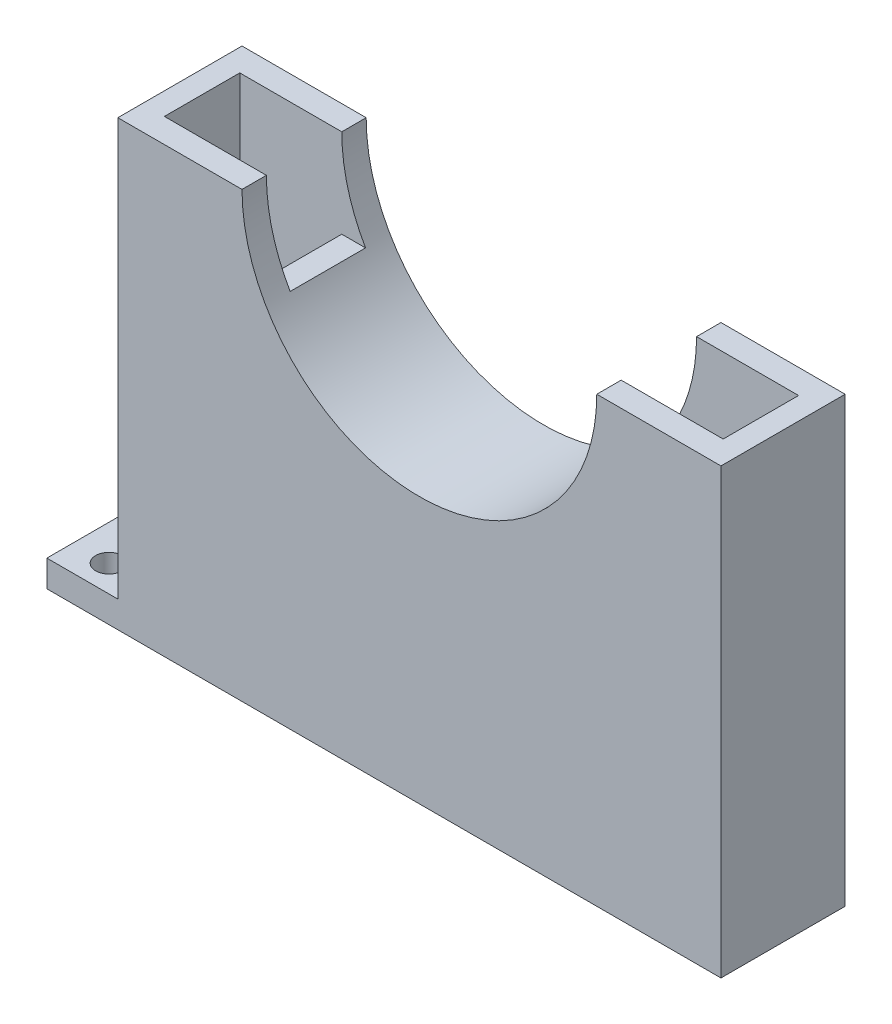
SolidWorks part; units mm, degrees
ref_plane "Front Plane" through (0, 0, 0) normal (0, 0, 1) x (1, 0, 0)
ref_plane "Top Plane" through (0, 0, 0) normal (0, 1, 0) x (1, 0, 0)
ref_plane "Right Plane" through (0, 0, 0) normal (1, 0, 0) x (0, 0, -1)
sketch "Sketch1" plane through (0, 0, 0) normal (0, 0, 1) x (1, 0, 0)
  line L0 (0, 0) -> (0, 3)
  line L1 (0, 3) -> (8, 3)
  line L2 (0, 0) -> (76, 0)
  line L3 (76, 0) -> (76, 50)
  line L4 (8, 3) -> (8, 50)
  line L5 (8, 50) -> (22, 50)
  line L6 (76, 50) -> (62, 50)
  arc A1 (62, 50) -> (22, 50) centre (42, 50) cw
  dimension "D1" = 14
  dimension "D2" = 20
  dimension "D3" = 3
  dimension "D4" = 50
  dimension "D5" = 8
extrude "Boss-Extrude1" add sketch "Sketch1" along normal blind 14
sketch "Sketch2" plane through (0, 0, 0) normal (0, -1, 0) x (1, 0, 0)
  line L0 (42, 14) -> (42, 0) construction
  line L1 (0, 14) -> (76, 14) construction
  line L2 (0, 0) -> (76, 0) construction
  line L3 (62, 14) -> (22, 14) construction
  line L4 (73.5, 11.25) -> (62, 11.25)
  line L5 (62, 11.25) -> (62, 2.75)
  line L6 (62, 2.75) -> (73.5, 2.75)
  line L7 (73.5, 2.75) -> (73.5, 11.25)
  line L10 (76, 14) -> (76, 0) construction
  line L11 (22, 2.75) -> (10.5, 2.75)
  line L12 (22, 11.25) -> (22, 2.75)
  line L13 (10.5, 11.25) -> (22, 11.25)
  line L14 (10.5, 2.75) -> (10.5, 11.25)
  point P14 (76, 7)
  point P15 (73.5, 7)
  dimension "D1" = 11.5
  dimension "D2" = 8.5
  dimension "D3" = 2.5
extrude "Cut-Extrude1" cut sketch "Sketch2" against normal up to surface (50 mm away) up to face at (15, 50, 7)
sketch "Sketch3" plane through (0, 3, 0) normal (0, 1, 0) x (1, 0, 0)
  line L0 (4, -3) -> (4, -11) construction
  line L1 (0, -14) -> (0, 0) construction
  line L4 (8, -14) -> (0, -14) construction
  circle A0 centre (4, -3) radius 1.5
  circle A1 centre (4, -11) radius 1.5
  point P7 (4, -14)
  point P10 (0, -7)
  point P11 (4, -7)
  dimension "D1" = 3
  dimension "D2" = 3
  dimension "D3" = 8
extrude "screw holes" cut sketch "Sketch3" against normal up to surface (3 mm away) up to face at (67.75, 0, 7)
sketch "Sketch4" plane through (0, 50, 0) normal (0, 1, 0) x (1, 0, 0)
  line L0 (8, -14) -> (76, -14) construction
  line L1 (10.5, -11.25) -> (73.5, -11.25)
  line L5 (73.5, -2.75) -> (73.5, -11.25)
  line L9 (10.5, -2.75) -> (10.5, -11.25)
  line L10 (10.5, -2.75) -> (73.5, -2.75)
  line L11 (10.5, -2.75) -> (10.5, -11.25) construction
extrude "Cut-Extrude2" cut sketch "Sketch4" against normal blind 10
